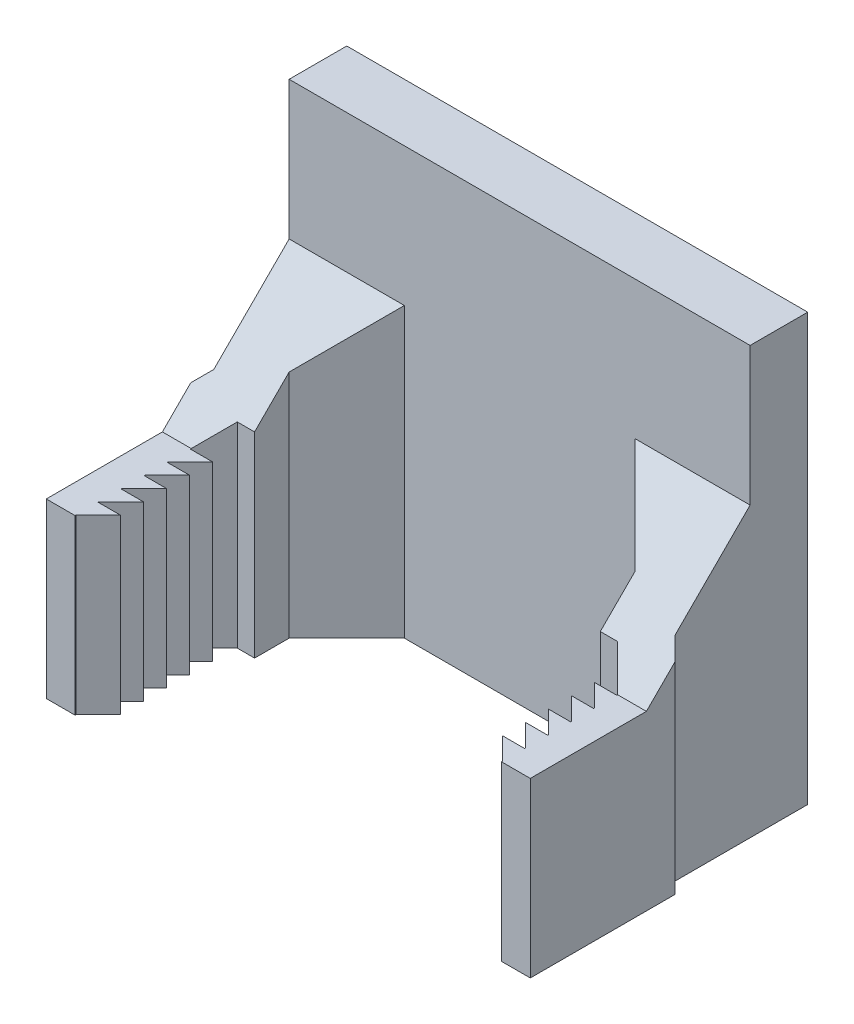
SolidWorks part; units mm, degrees
ref_plane "Front Plane" through (0, 0, 0) normal (0, 0, 1) x (1, 0, 0)
ref_plane "Top Plane" through (0, 0, 0) normal (0, 1, 0) x (1, 0, 0)
ref_plane "Right Plane" through (0, 0, 0) normal (1, 0, 0) x (0, 0, -1)
sketch "Sketch2" plane through (0, 0, 0) normal (0, 1, 0) x (1, 0, 0)
  line L0 (-13.5, 0) -> (6.5, 0)
  line L5 (11.5, -5) -> (11.5, -41)
  line L6 (11.5, -41) -> (31.9173, -41)
  line L7 (31.9173, -41) -> (31.9173, -35.699)
  line L8 (31.9173, -35.699) -> (16.5, -35.699)
  line L9 (16.5, -35.699) -> (16.5, 5)
  line L10 (16.5, 5) -> (-23.5, 5)
  line L11 (-23.5, 5) -> (-23.5, -35.699)
  line L12 (-23.5, -35.699) -> (-38.9173, -35.699)
  line L13 (-38.9173, -35.699) -> (-38.9173, -41)
  line L14 (-38.9173, -41) -> (-18.5, -41)
  line L15 (-18.5, -41) -> (-18.5, -5)
  line L16 (-23.5, -35.699) -> (-23.5, -53.6584) construction
  line L17 (-29.5, -29.038) -> (-29.5, -53.6584) construction
  line L18 (-29.5, -47.6505) -> (-23.5, -47.6505) construction
  line L19 (-3.5, 0) -> (-3.5, -26.0929) construction
  line L20 (-26.5, -47.6505) -> (-26.5, -68.2741) construction
  line L21 (23.5, -24.9282) -> (23.5, -62.6056) construction
  line L22 (20.5, -24.4655) -> (20.5, -49.1581) construction
  line L23 (26.5, -24.4655) -> (26.5, -49.1581) construction
  line L24 (20.5, -44.8687) -> (26.5, -44.8687) construction
  line L25 (23.5, -44.8687) -> (23.5, -42.6651) construction
  line L26 (-18.5, -5) -> (-13.5, 0)
  line L27 (6.5, 0) -> (11.5, -5)
  point P0 (-18.5, 0)
  point P1 (11.5, 0)
  point P23 (-3.5, -23.0301)
  point P34 (23.5, -43.7669)
  dimension "D1" = 30
  dimension "D2" = 5
  dimension "D3" = 5
  dimension "D4" = 46
  dimension "D5" = 6
  dimension "D6" = 50
  dimension "D7" = 6
extrude "Boss-Extrude1" add sketch "Sketch2" along normal blind 15
sketch "Sketch3" plane through (0, 0, 35.699) normal (0, 0, -1) x (-1, 0, 0)
  line L0 (-31.9173, 9) -> (43.2878, 9) construction
  line L1 (-31.9173, 15) -> (-31.9173, 0) construction
  line L2 (-16.5, 15) -> (23.5, 15) construction
  line L3 (-23.5, 15) -> (26.5, 15) construction
  line L4 (23.5, 15) -> (38.9173, 15) construction
  line L6 (-23.5, 15) -> (-23.5, -3.7562) construction
  line L7 (26.5, 15) -> (26.5, -7.565) construction
  line L8 (23.5, 15) -> (23.5, 0) construction
  circle A0 centre (26.5, 9) radius 3.05
  circle A1 centre (-23.5, 9) radius 3.05
  point P11 (1.5, 15)
  dimension "D4" = 6.1
  dimension "D1" = 6
  dimension "D2" = 50
  dimension "D3" = 3
extrude "Cut-Extrude1" cut sketch "Sketch3" against normal blind 15
sketch "Sketch4" plane through (0, 15, 0) normal (0, 1, 0) x (1, 0, 0)
  line L0 (-13.0972, 0) -> (6.5, 0) construction
  line L1 (-13.5, 0) -> (6.5, 0) construction
  line L2 (6.5, 0) -> (11.5, -5) construction
  line L3 (-23.5, -10) -> (18.1067, -10) construction
  line L4 (-23.5, 5) -> (-23.5, -35.699) construction
  line L5 (-23.5, -25.7032) -> (-18.5, -25.7032) construction
  line L6 (-18.5, -41) -> (-18.5, -5) construction
  line L7 (-21, -25.7032) -> (-21, 5) construction
  line L8 (16.5, 5) -> (-23.5, 5) construction
  line L9 (-20, 2.3375) -> (-20, -23.3678) construction
  line L10 (-22, 3.2587) -> (-22, -23.3678) construction
  line L11 (-23.5, -12) -> (-15.7746, -12) construction
  line L12 (-20.075, -10.075) -> (-22, -12)
  line L13 (-22, -12) -> (-20, -12) construction
  line L14 (-20.075, -12.075) -> (-22, -14)
  line L15 (-20, -16.075) -> (-18.4226, -16.075)
  line L16 (-20.075, -14.075) -> (-22, -16)
  line L17 (-22, -20.075) -> (-23.6463, -20.075)
  line L18 (-20.075, -16.075) -> (-22, -18)
  line L19 (-21.925, -18) -> (-20, -18)
  line L20 (-20.075, -18.075) -> (-22, -20)
  line L21 (-21.925, -20) -> (-20, -20)
  line L22 (-20, -20) -> (-20, -28.575)
  line L23 (-22, -12.075) -> (-20.075, -12.075)
  line L24 (-18.5, -19.4434) -> (-18.5, -20.4817) construction
  line L25 (-22, -14.075) -> (-20.075, -14.075)
  line L26 (-23.6463, -20.075) -> (-45.6004, -20.075)
  line L27 (-22, -16.075) -> (-20.075, -16.075)
  line L28 (-20, -16.075) -> (-21.925, -18)
  line L29 (-22, -18.075) -> (-20.075, -18.075)
  line L30 (-20, -18.075) -> (-21.925, -20)
  line L31 (-3.5, 5) -> (-3.5, -13.3571) construction
  line L34 (-22, -12) -> (-22, -12.075)
  line L35 (-22, -14) -> (-22, -14.075)
  line L36 (-22, -16) -> (-22, -16.075)
  line L37 (-22, -18) -> (-22, -18.075)
  line L38 (-22, -20) -> (-22, -20.075)
  line L39 (-20, -18) -> (-20, -18.075)
  line L40 (13.075, -10.075) -> (15, -12)
  line L41 (15, -12) -> (15, -12.075)
  line L42 (15, -12.075) -> (13.075, -12.075)
  line L43 (-3.2986, 0) -> (-3.2986, -36.5088) construction
  line L44 (-21.925, -16) -> (-21, -16)
  line L45 (-21.925, -14) -> (-21, -14)
  line L46 (13.075, -12.075) -> (15, -14)
  line L47 (15, -14) -> (15, -14.075)
  line L48 (15, -14.075) -> (13.075, -14.075)
  line L49 (15, -16) -> (15, -16.075)
  line L50 (13.075, -14.075) -> (15, -16)
  line L51 (15, -16.075) -> (13.075, -16.075)
  line L52 (13.075, -16.075) -> (15, -18)
  line L53 (15, -18) -> (15, -18.075)
  line L54 (15, -18.075) -> (13.075, -18.075)
  line L55 (13.075, -18.075) -> (15, -20)
  line L56 (15, -20) -> (15, -20.075)
  line L57 (15, -20.075) -> (16.6463, -20.075)
  line L59 (-45.6004, -20.075) -> (-45.6004, -48.4062)
  line L60 (-45.6004, -48.4062) -> (39.6716, -48.4062)
  line L61 (39.6716, -48.4062) -> (39.6716, -20.075)
  line L62 (39.6716, -20.075) -> (16.6463, -20.075)
  line L63 (-20, -8) -> (-22, -10)
  line L64 (-22, -10) -> (-22, -10.075)
  line L65 (-22, -10.075) -> (-20.075, -10.075)
  line L66 (15, -10.075) -> (13.075, -10.075)
  line L67 (15, -10) -> (15, -10.075)
  line L68 (13, -8) -> (15, -10)
  line L69 (-20, -8) -> (13, -8)
  dimension "D1" = 10
  dimension "D2" = 1
  dimension "D3" = 1
  dimension "D4" = 2
  dimension "D6" = 8.575
  dimension "D7" = 2
  dimension "D5" = 5
extrude "Cut-Extrude3" cut sketch "Sketch4" against normal through all
sketch "Sketch5" plane through (-23.5, 0, 0) normal (-1, 0, 0) x (0, 0, 1)
  line L0 (-5, 15) -> (20.075, 15) construction
  line L1 (20.075, 0) -> (7.5375, 0)
  line L2 (20.075, 0) -> (20.075, 15)
  line L3 (20.075, 15) -> (7.5375, 15)
  line L4 (7.5375, 0) -> (7.5375, 15)
extrude "Boss-Extrude2" add sketch "Sketch5" along normal blind 1
ref_plane "Plane1" through (-3.5, 0, 0) normal (1, 0, 0) x (0, 0, -1)
mirror "Mirror1" about plane through (-3.5, 0, 0) normal (1, 0, 0) of "Boss-Extrude2"
chamfer "Chamfer1" distance 1 angle 45 2 edges at (16.5, 7.5, 7.5375) (-23.5, 7.5, 7.5375)
sketch "Sketch6" plane through (0, 0, -5) normal (0, 0, -1) x (-1, 0, 0)
  line L0 (-16.5, 0) -> (23.5, 0)
  line L1 (23.5, 0) -> (23.5, 37)
  line L2 (23.5, 37) -> (-16.5, 37)
  line L3 (-16.5, 37) -> (-16.5, 0)
  dimension "D1" = 37
extrude "Boss-Extrude3" add sketch "Sketch6" against normal up to surface (5 mm away) up to face at (-3.5, 7.5, 0)
chamfer "Chamfer2" distance 10 angle 45 2 edges at (11.5, 15, 0) (-18.5, 15, 0)
